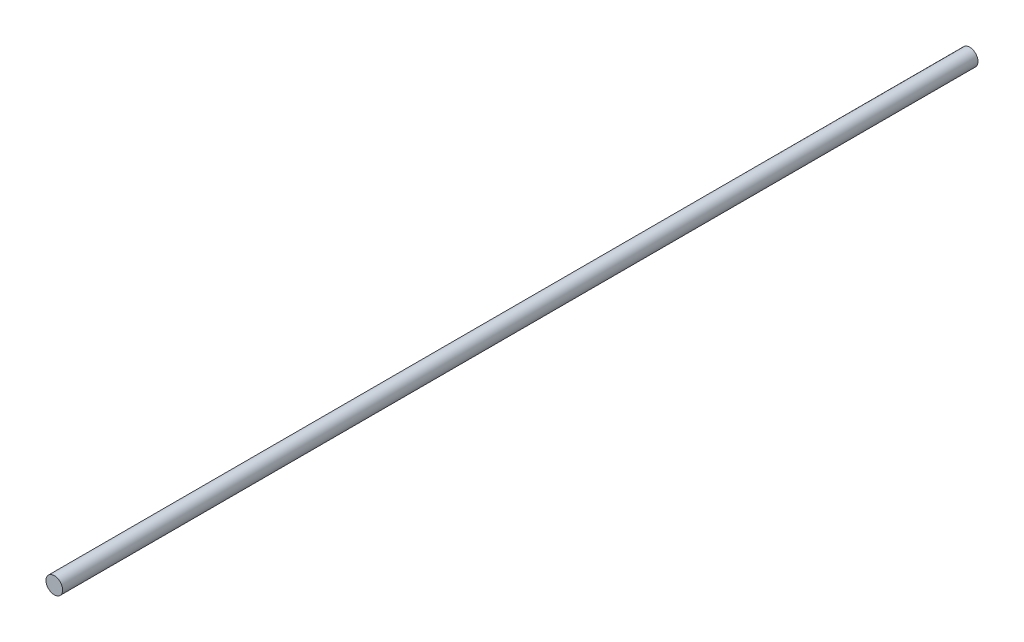
SolidWorks part; units mm, degrees
ref_plane "Front Plane" through (0, 0, 0) normal (0, 0, 1) x (1, 0, 0)
ref_plane "Top Plane" through (0, 0, 0) normal (0, 1, 0) x (1, 0, 0)
ref_plane "Right Plane" through (0, 0, 0) normal (1, 0, 0) x (0, 0, -1)
sketch "Sketch1" plane through (0, 0, 0) normal (0, 0, 1) x (1, 0, 0)
  circle A0 centre (0, 0) radius 2
  dimension "D1" = 4
extrude "Boss-Extrude1" add sketch "Sketch1" along normal blind 110 and the other way blind 110
